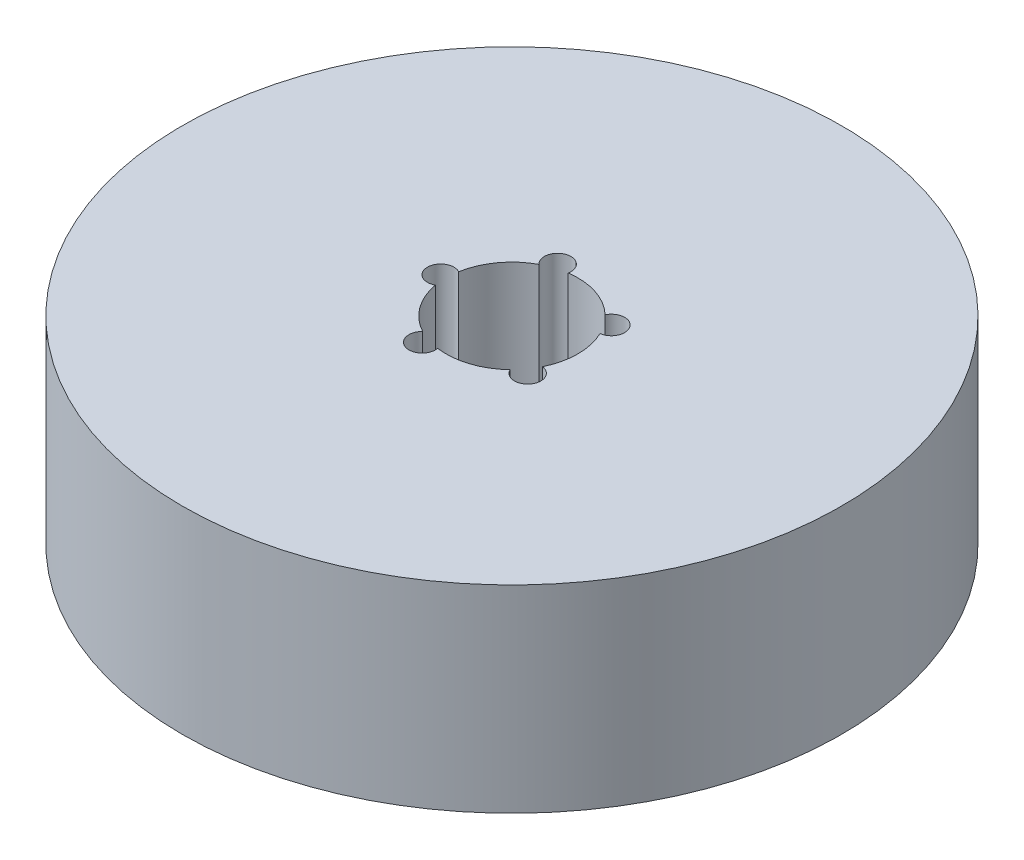
SolidWorks part; units mm, degrees
ref_plane "Front Plane" through (0, 0, 0) normal (0, 0, 1) x (1, 0, 0)
ref_plane "Top Plane" through (0, 0, 0) normal (0, 1, 0) x (1, 0, 0)
ref_plane "Right Plane" through (0, 0, 0) normal (1, 0, 0) x (0, 0, -1)
sketch "Sketch1" plane through (0, 0, 0) normal (0, 1, 0) x (1, 0, 0)
  circle A0 centre (0, 0) radius 50
  dimension "FLANGE_OD" = 100
extrude "Boss-Extrude1" add sketch "Sketch1" along normal blind 30
sketch "Sketch2" plane through (0, 0, 0) normal (0, 1, 0) x (1, 0, 0)
  circle A0 centre (0, 0) radius 10
  dimension "BORE_D" = 20
extrude "Cut-Extrude1" cut sketch "Sketch2" along normal through all
sketch "Sketch3" plane through (0, 30, 0) normal (0, 1, 0) x (1, 0, 0)
  circle A0 centre (0, 0) radius 10.8042 construction
  circle A1 centre (-10.8042, 0) radius 2.009
  dimension "BOLT_D" = 4.018
  dimension "BOLT_PCD" = 21.6085
extrude "Cut-Extrude2" cut sketch "Sketch3" against normal blind 25.1474
pattern_circular "CirPattern1" count 5 over 360 about axis through (0, 0, 0) along (0, 1, 0) of "Cut-Extrude2"
